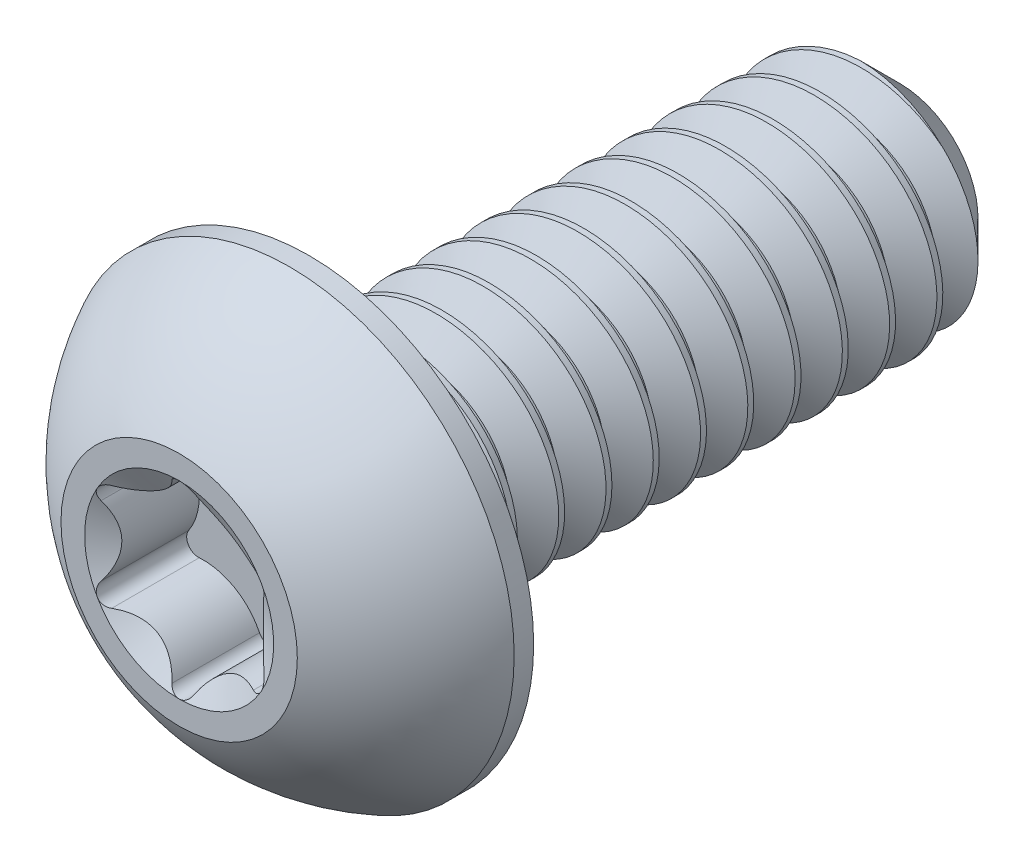
SolidWorks part; units mm, degrees
material "Passivated 18-8 Stainless Steel"
ref_plane "Front" through (0, 0, 0) normal (0, 0, 1) x (1, 0, 0)
ref_plane "Top" through (0, 0, 0) normal (0, 1, 0) x (1, 0, 0)
ref_plane "Right" through (0, 0, 0) normal (1, 0, 0) x (0, 0, -1)
sketch "Sketch1" plane through (0, 0, 0) normal (1, 0, 0) x (0, 0, -1)
  line L2 (1.1, 1) -> (6.1, 1)
  line L3 (6.1, 1) -> (6.1, 0)
  line L4 (6.1, 0) -> (1.1, 0)
  line L6 (0.935, 1.9) -> (1.1, 1.9) construction
  line L7 (6.1, 1) -> (6.1, -1) construction
  line L8 (0, 0) -> (1.1, 0) construction
  line L9 (1.1, 1.9) -> (1.1, -1.9) construction
  line L11 (1.1, 1) -> (1.1, 0)
  line L14 (0, 0) -> (0, 1) construction
  arc A3 (0, 1) -> (0.935, 1.9) centre (1.8632, 0) cw construction
  dimension "D1" = 0.165
revolve "Revolve1" add sketch "Sketch1" angle 360 mid plane about L4
sketch "Sketch3" plane through (0, 0, -6.1) normal (0, 0, -1) x (-1, 0, 0)
  circle A0 centre (0, 0) radius 1
curve "Helix/Spiral1" pitch 0.4 height 5 turns 12.5
chamfer "Chamfer1" distance 0.34 angle 45 1 edges at (0, 1, -6.1)
sketch "Sketch2" plane through (0, 0, 0) normal (1, 0, 0) x (0, 0, -1)
  line L0 (5.76, 1) -> (6.11, 1)
  line L1 (6.11, 1) -> (5.96, 0.7402)
  line L2 (5.96, 0.7402) -> (5.91, 0.7402)
  line L3 (5.91, 0.7402) -> (5.76, 1)
  line L4 (5.835, 0.8701) -> (6.035, 0.8701) construction
  dimension "D1" = 60
  dimension "D2" = 0.05
  dimension "D3" = 0.2
sweep "Cut-Sweep1" cut profiles "Sketch2" path "Helix/Spiral1"
sketch "Sketch7" plane through (0, 0, 0) normal (1, 0, 0) x (0, 0, -1)
  line L0 (0, 0) -> (0, 1) construction
  line L6 (0.935, 1.9) -> (1.1, 1.9) construction
  line L8 (0, 0) -> (1.1, 0) construction
  line L11 (1.1, 1.9) -> (1.1, -1.9) construction
  line L12 (0.935, 1.9) -> (1.1, 1.9)
  line L13 (0, 0) -> (1.1, 0)
  line L15 (1.1, 1.9) -> (1.1, 0)
  line L16 (0, 1) -> (0, 0)
  arc A2 (0.935, 1.9) -> (0, 1) centre (1.8632, 0) ccw construction
  arc A3 (0.935, 1.9) -> (0, 1) centre (1.8632, 0) ccw
revolve "Revolve2" add sketch "Sketch7" angle 360 mid plane about L13
sketch "Sketch5" plane through (0, 0, 0) normal (0, 0, 1) x (1, 0, 0)
  line L0 (1.5926, 0) -> (-1.5926, 0) construction
  line L2 (0, 0) -> (-0.6928, 0.4)
  line L3 (0, 0) -> (-0.6928, -0.4)
  line L4 (0, 0.8) -> (0, 0.7) construction
  line L5 (0, 0.7) -> (0, 0.6) construction
  circle A0 centre (0, 0) radius 0.6 construction
  circle A1 centre (0, 0) radius 0.7 construction
  circle A2 centre (0, 0) radius 0.8 construction
  arc A3 (-0.6894, 0.2944) -> (-0.6894, -0.2944) centre (-1.1298, 0) cw
  arc A4 (-0.6894, 0.2944) -> (-0.6928, 0.4) centre (-0.6062, 0.35) cw
  arc A5 (-0.6894, -0.2944) -> (-0.6928, -0.4) centre (-0.6062, -0.35) ccw
  dimension "D4" = 1.2
  dimension "D2" = 1.6
  dimension "D1" = 30
extrude "Cut-Extrude2" cut sketch "Sketch5" against normal blind 0.77
pattern_circular "CirPattern1" count 6 over 360 about axis through (0, 0, 0) along (0, 0, 1) of "Cut-Extrude2"
sketch "Sketch11" plane through (0, 0, 0) normal (0, 0, 1) x (1, 0, 0)
  circle A0 centre (0, 0) radius 0.8 construction
  circle A1 centre (0, 0) radius 0.8
extrude "Cut-Extrude3" cut sketch "Sketch11" against normal blind 0.77 draft 60
sketch "Sketch9" [suppressed] plane through (0, 0, -1.4986) normal (0, 0, 1) x (1, 0, 0)
  circle A2 centre (0, 0) radius 1.4224
extrude "Boss-Extrude2" [suppressed] add sketch "Sketch9" against normal offset from surface (7.0104 mm away) 31.75
sketch "Sketch10" plane through (0, 0, 0) normal (1, 0, 0) x (0, 0, -1)
  line L0 (6.1, 1) -> (6.1, -1) construction
  point P0 (5.5, -1)
  dimension "D1" = 0.6
equation "\"D3@Helix/Spiral1\"=\"Lg@Sketch1\" "
equation "\"D2@Sketch2\" = \"D4@Helix/Spiral1\" * .125"
equation "\"D3@Sketch2\" = \"D4@Helix/Spiral1\" * .5"
equation "\"D1@Chamfer1\"=\"D4@Helix/Spiral1\" *.850"
equation "\"D1@Cut-Extrude2\" = \"Head Ht@Sketch1\" * .7"
equation "\"D1@Sketch1\" = \"Head Ht@Sketch1\" * .15"
equation "\"D1@Sketch10\" = \"D4@Helix/Spiral1\" * 1.5"
equation "\"D1@Cut-Extrude3\" = \"D1@Cut-Extrude2\""
equation "\"D2@Sketch5\" = \"Dia@Sketch1\" * .8"
equation "\"D4@Sketch5\" = \"D2@Sketch5\" * .75"
